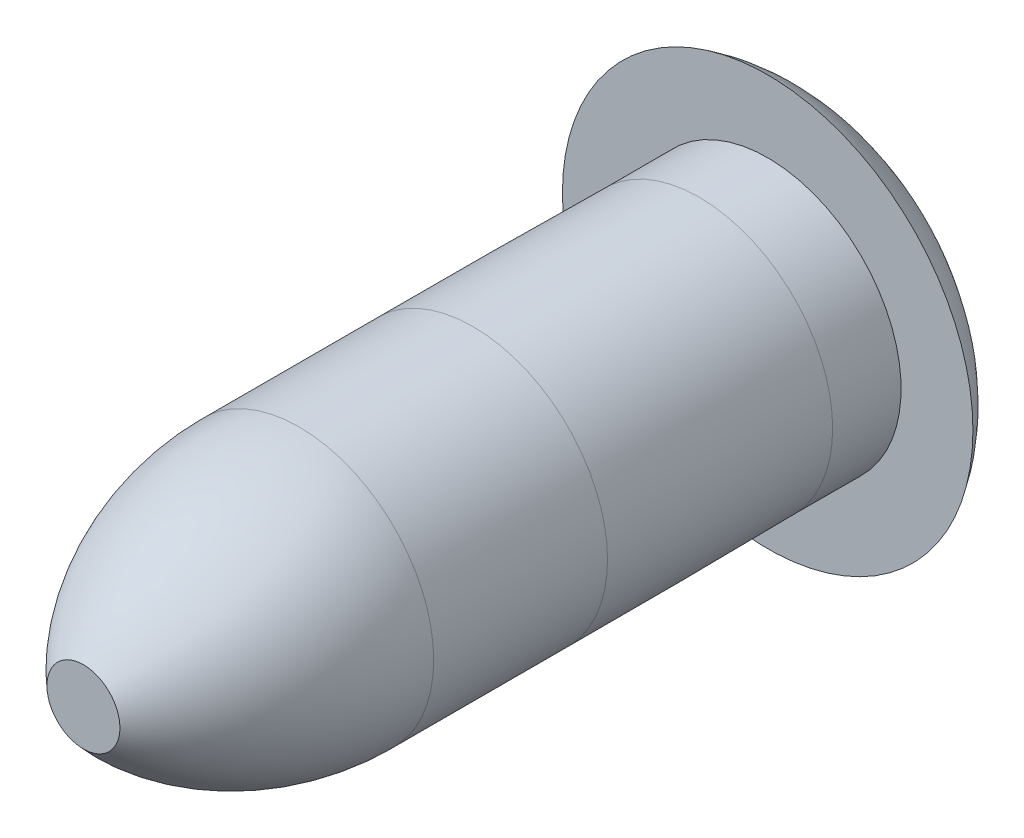
SolidWorks part; units mm, degrees
ref_plane "Front Plane" through (0, 0, 0) normal (0, 0, 1) x (1, 0, 0)
ref_plane "Top Plane" through (0, 0, 0) normal (0, 1, 0) x (1, 0, 0)
ref_plane "Right Plane" through (0, 0, 0) normal (1, 0, 0) x (0, 0, -1)
sketch "Sketch1" plane through (0, 0, 0) normal (0, 0, 1) x (1, 0, 0)
  circle A0 centre (0, 0) radius 2.925
  dimension "D1" = 5.85
extrude "Boss-Extrude1" add sketch "Sketch1" along normal blind 1.5
sketch "Sketch2" plane through (0, 0, 0) normal (0, 1, 0) x (1, 0, 0)
  line L0 (0, 1.4) -> (2, 1.4)
  line L1 (0, 1.4) -> (0, 0)
  line L2 (0, 0) -> (4.5, 0)
  arc A0 (2, 1.4) -> (4.5, 0) centre (2, -1.5321) cw
  dimension "D1" = 4.5
  dimension "D2" = 1.4
  dimension "D3" = 2
revolve "Revolve1" add sketch "Sketch2" angle 360 about L1
sketch "Sketch3" plane through (0, 0, 0) normal (0, 1, 0) x (1, 0, 0)
  line L0 (0, 0) -> (0, -15)
  line L1 (0, -15) -> (0.8, -15)
  line L2 (0.8, -15) -> (0.8, 0)
  line L3 (0.8, 0) -> (0, 0)
  line L4 (2.95, -6.4606) -> (2.95, -10.2715)
  line L5 (0, -1.595) -> (0, 1.595) construction
  line L6 (2.55, -6.7247) -> (2.55, -10.6756)
  line L7 (-2.925, -1.5) -> (2.925, -1.5) construction
  line L8 (0.8, -1.5) -> (0.8, 0)
  line L9 (2.925, 0) -> (2.925, -1.5)
  line L10 (-2.925, 0) -> (2.925, 0) construction
  line L11 (0.8, -14.6) -> (0.8, -15)
  line L12 (0.8, 0) -> (2.925, 0)
  arc A0 (2.95, -6.4606) -> (2.925, -1.5) centre (-489.2178, -6.4606) ccw
  arc A1 (2.55, -6.7247) -> (0.8, -1.5) centre (-6.1242, -6.7247) ccw
  arc A2 (2.95, -10.2715) -> (0.8, -15) centre (-3.3247, -10.2715) cw
  arc A3 (2.55, -10.6756) -> (0.8, -14.6) centre (-2.7253, -10.6756) cw
  dimension "D5" = 0.4
  dimension "D1" = 15
  dimension "D2" = 0.8
  dimension "D3" = 2.95
  dimension "D4" = 0.4
revolve "Revolve3" add sketch "Sketch3" angle 360 about L0 region at (0.4, 0, 7.5) region at (1.8625, 0, 0.1515)
